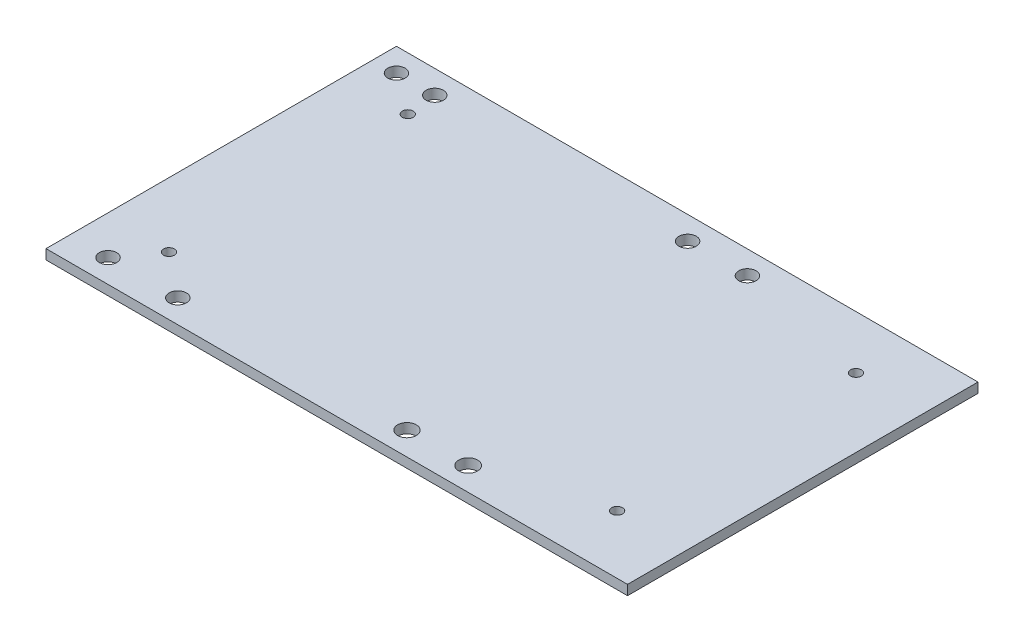
SolidWorks part; units mm, degrees
ref_plane "Front Plane" through (0, 0, 0) normal (0, 0, 1) x (1, 0, 0)
ref_plane "Top Plane" through (0, 0, 0) normal (0, 1, 0) x (1, 0, 0)
ref_plane "Right Plane" through (0, 0, 0) normal (1, 0, 0) x (0, 0, -1)
sketch "Sketch1" plane through (0, 0, 0) normal (0, 1, 0) x (1, 0, 0)
  line L0 (15, -15) -> (39.6804, -15) construction
  line L1 (0, 0) -> (375, 0)
  line L2 (0, 0) -> (0, -226)
  line L3 (0, -226) -> (375, -226)
  line L4 (375, 0) -> (375, -226)
  line L5 (25, -211) -> (70, -211) construction
  line L6 (241.3, -15) -> (202.7575, -15) construction
  line L7 (217.7575, -211) -> (257.2443, -211) construction
  line L8 (41.5666, -34.2814) -> (41.5666, -188.2814) construction
  line L9 (41.5666, -188.2814) -> (330.5666, -188.2814) construction
  line L10 (330.5666, -188.2814) -> (330.5666, -34.2814) construction
  line L11 (330.5666, -34.2814) -> (41.5666, -34.2814) construction
  line L12 (41.5666, -34.2814) -> (33.5666, -34.2814) construction
  line L13 (330.5666, -34.2814) -> (330.5666, -26.2814) construction
  line L14 (330.5666, -188.2814) -> (330.5666, -196.2814) construction
  circle A0 centre (15, -15) radius 5.5818
  circle A1 centre (39.6804, -15) radius 5.5818
  circle A2 centre (25, -211) radius 5.5818
  circle A3 centre (70, -211) radius 5.5818
  circle A4 centre (241.3, -15) radius 5.5818
  circle A5 centre (202.7575, -15) radius 5.5818
  circle A6 centre (217.7575, -211) radius 6.0182
  circle A7 centre (257.2443, -211) radius 6.107
  circle A8 centre (41.5666, -34.2814) radius 3.5
  circle A9 centre (41.5666, -188.2814) radius 3.5
  circle A10 centre (330.5666, -188.2814) radius 3.5
  circle A11 centre (330.5666, -34.2814) radius 3.5
  dimension "D10" = 7
  dimension "D1" = 45
  dimension "D2" = 25
  dimension "D3" = 15
  dimension "D4" = 15
  dimension "D5" = 15
  dimension "D6" = 375
  dimension "D7" = 226
  dimension "D8" = 241.3
  dimension "D9" = 15
  dimension "D11" = 289
  dimension "D12" = 154
  dimension "D13" = 8
  dimension "D14" = 33.5666
  dimension "D15" = 8
  dimension "D16" = 26.2814
  dimension "D17" = 8
extrude "Boss-Extrude1" add sketch "Sketch1" against normal blind 6.35
